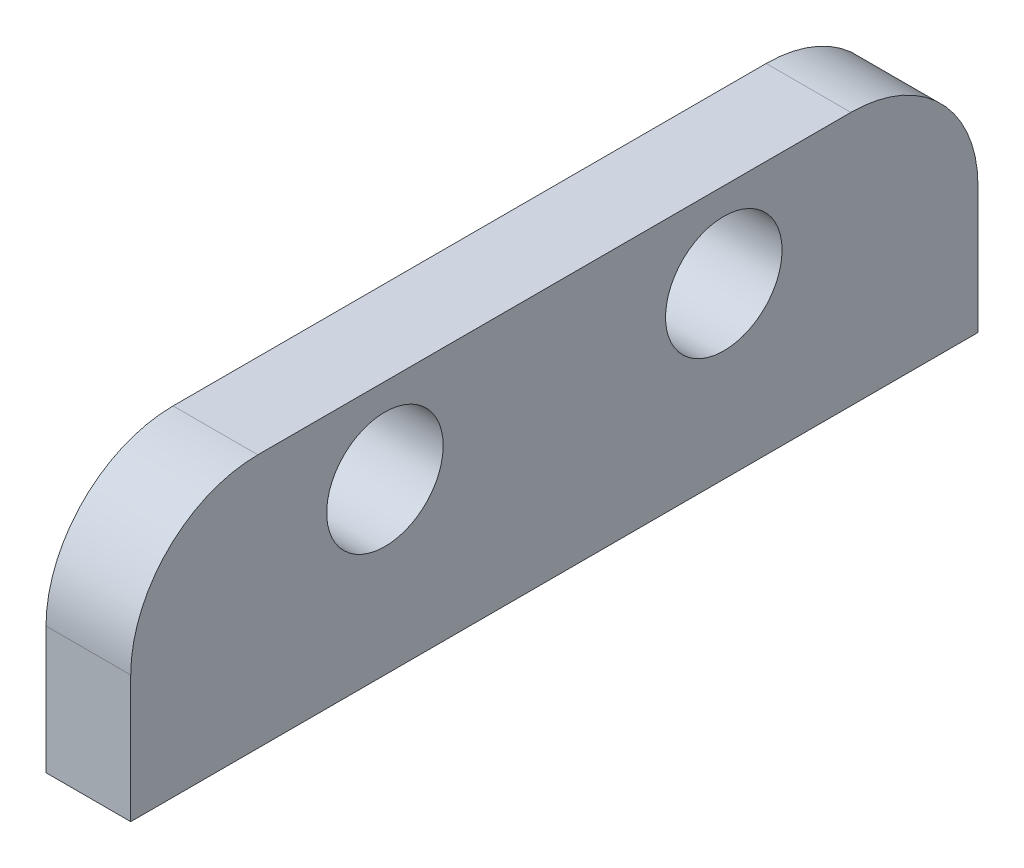
SolidWorks part; units mm, degrees
ref_plane "Front Plane" through (0, 0, 0) normal (0, 0, 1) x (1, 0, 0)
ref_plane "Top Plane" through (0, 0, 0) normal (0, 1, 0) x (1, 0, 0)
ref_plane "Right Plane" through (0, 0, 0) normal (1, 0, 0) x (0, 0, -1)
sketch "Sketch1" plane through (0, 0, 0) normal (1, 0, 0) x (0, 0, -1)
  line L0 (-8, 2) -> (8, 2) construction
  line L1 (20, -6) -> (-20, -6)
  line L2 (20, -6) -> (20, 6)
  line L3 (20, 6) -> (-20, 6)
  line L4 (-20, -6) -> (-20, 6)
  line L5 (20, -6) -> (-20, 6) construction
  line L6 (20, 6) -> (-20, -6) construction
  line L7 (8, 2) -> (8, -6) construction
  line L8 (0, 2) -> (0, 0) construction
  circle A0 centre (-8, 2) radius 2.75
  circle A1 centre (8, 2) radius 2.75
  point P0 (0, 0)
  dimension "D5" = 5.5
  dimension "D1" = 40
  dimension "D2" = 12
  dimension "D3" = 8
  dimension "D4" = 16
extrude "Boss-Extrude1" add sketch "Sketch1" along normal blind 4
fillet "Fillet1" radius 6 2 edges at (2, 6, 20) (2, 6, -20)
